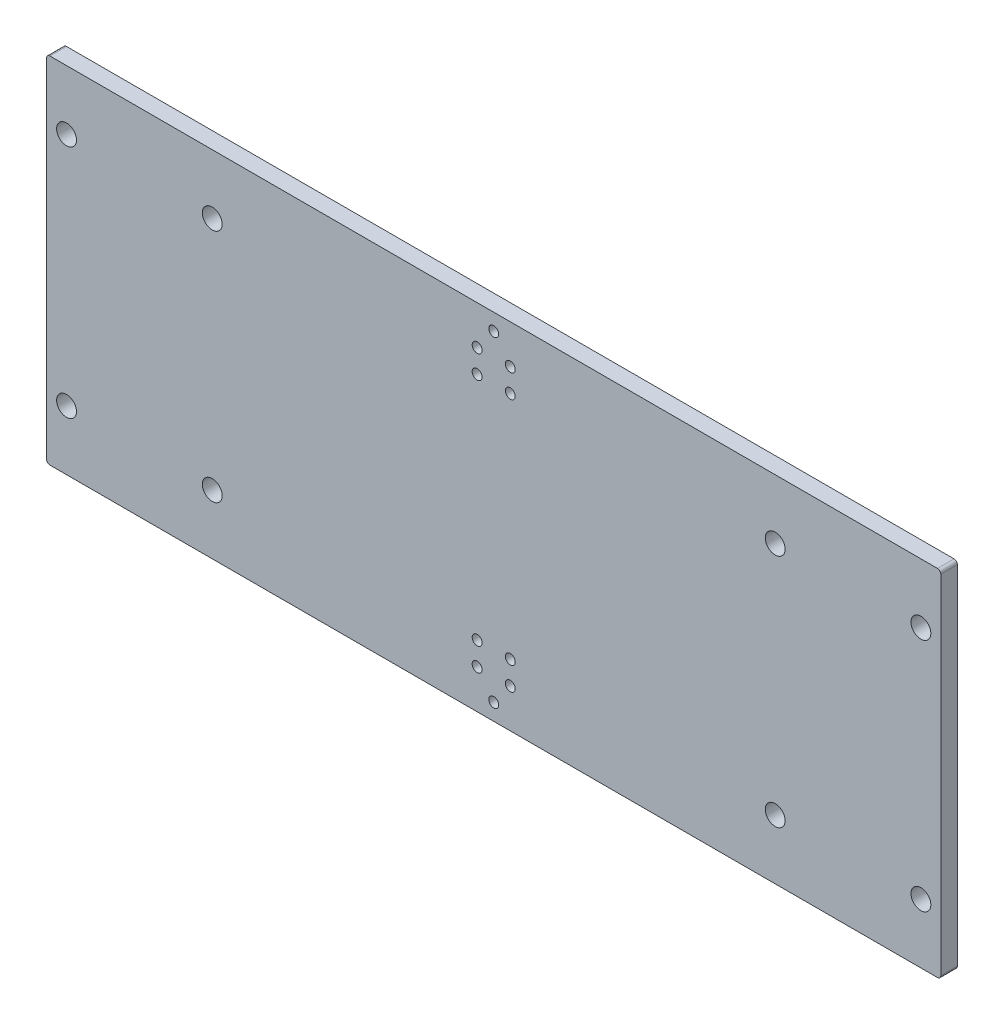
SolidWorks part; units mm, degrees
ref_plane "前视基准面" through (0, 0, 0) normal (0, 0, 1) x (1, 0, 0)
ref_plane "上视基准面" through (0, 0, 0) normal (0, 1, 0) x (1, 0, 0)
ref_plane "右视基准面" through (0, 0, 0) normal (1, 0, 0) x (0, 0, -1)
sketch "草图1" plane through (0, 0, 0) normal (0, 0, 1) x (1, 0, 0)
  line L1 (-135, -53.5) -> (135, -53.5)
  line L2 (-135, -53.5) -> (-135, 53.5)
  line L3 (-135, 53.5) -> (135, 53.5)
  line L4 (135, -53.5) -> (135, 53.5)
  line L5 (-135, -53.5) -> (135, 53.5) construction
  line L6 (-135, 53.5) -> (135, -53.5) construction
  point P0 (0, 0)
  dimension "D1" = 270
  dimension "D2" = 107
base flange "基体-法兰1" sketch "草图1" thickness 5 reverse thickness direction no parameters "D1"=0.7366
sketch "草图6" plane through (0, 0, 0) normal (0, 0, 1) x (1, 0, 0)
  line L0 (-135, 53.5) -> (-135, -53.5) construction
  line L1 (-135, -53.5) -> (135, -53.5) construction
  line L2 (135, 53.5) -> (-135, 53.5) construction
  circle A0 centre (-129, 35.5) radius 3
  circle A1 centre (-129, -35.5) radius 3
  circle A2 centre (-85, 35.5) radius 3
  circle A3 centre (-85, -35.5) radius 3
  dimension "D2" = 6
  dimension "D3" = 6
  dimension "D7" = 6
  dimension "D8" = 6
  dimension "D1" = 6
  dimension "D4" = 6
  dimension "D5" = 18
  dimension "D6" = 18
  dimension "D9" = 44
  dimension "D10" = 44
extrude "切除-拉伸1" cut sketch "草图6" against normal blind 10 normal cut yes
mirror "镜向1" about plane through (0, 0, 0) normal (1, 0, 0) of "切除-拉伸1"
sketch "草图7" plane through (0, 0, 0) normal (0, 0, 1) x (1, 0, 0)
  line L0 (135, 53.5) -> (-135, 53.5) construction
  circle A0 centre (0, 48.5) radius 1.5
  dimension "D1" = 3
  dimension "D2" = 5
extrude "切除-拉伸2" cut sketch "草图7" against normal blind 10 normal cut yes
mirror "镜向2" about plane through (0, 0, 0) normal (0, 1, 0) of "切除-拉伸2"
fillet "圆角1" radius 1 4 edges at (-135, -53.5, -2.5) (-135, 53.5, -2.5) (135, -53.5, -2.5) (135, 53.5, -2.5)
sketch "草图8" plane through (0, 0, -5) normal (0, 0, -1) x (-1, 0, 0)
  line L0 (-134, 53.5) -> (134, 53.5) construction
  circle A0 centre (-5, 41.75) radius 1.5
  circle A1 centre (5, 41.75) radius 1.5
  circle A2 centre (5, 34.75) radius 1.5
  circle A3 centre (-5, 34.75) radius 1.5
  circle A4 centre (0, 48.5) radius 1.5 construction
  dimension "D1" = 3
  dimension "D2" = 3
  dimension "D3" = 3
  dimension "D4" = 3
  dimension "D5" = 11.75
  dimension "D6" = 11.75
  dimension "D7" = 7
  dimension "D8" = 7
  dimension "D9" = 5
  dimension "D10" = 5
extrude "切除-拉伸3" cut sketch "草图8" against normal blind 10 normal cut yes
mirror "镜向3" about plane through (0, 0, 0) normal (0, 1, 0) of "切除-拉伸3"
sketch "折弯-线1" [suppressed] plane through (0, 0, 0) normal (0, 1, 0) x (1, 0, 0)
sketch "边界框1" [suppressed] plane through (0, 0, 0) normal (0, 1, 0) x (1, 0, 0)
sheet metal parameters "钣金1" thickness 5 parameters "D1"=0.7366
flat pattern "平板型式1" [suppressed]
sketch "折弯-线2" plane through (0, 0, 0) normal (0, 1, 0) x (1, 0, 0)
sketch3d "边界框2" [suppressed]
  line L0 (150, -53.5, 0) -> (-150, -53.5, 0) construction
  line L1 (150, 53.5, 0) -> (-150, 53.5, 0) construction
  line L2 (150, -53.5, 0) -> (150, 53.5, 0) construction
  line L3 (-150, -53.5, 0) -> (-150, 53.5, 0) construction
sheet metal parameters "钣金2" thickness 5 parameters "D1"=0.7366
flat pattern "平板型式1"
sketch "折弯-线2" plane through (0, 0, 0) normal (0, 1, 0) x (1, 0, 0)
sketch3d "边界框2" [suppressed]
  line L0 (-150, -53.5, 0) -> (150, -53.5, 0) construction
  line L1 (-150, 53.5, 0) -> (150, 53.5, 0) construction
  line L2 (-150, -53.5, 0) -> (-150, 53.5, 0) construction
  line L3 (150, -53.5, 0) -> (150, 53.5, 0) construction
sheet metal parameters "钣金3" thickness 5 parameters "D1"=0.7366
flat pattern "平板型式1"
sketch "折弯-线2" plane through (0, 0, 0) normal (0, 1, 0) x (1, 0, 0)
sketch3d "边界框2" [suppressed]
  line L0 (-135, -53.5, 0) -> (135, -53.5, 0) construction
  line L1 (-135, 53.5, 0) -> (135, 53.5, 0) construction
  line L2 (-135, -53.5, 0) -> (-135, 53.5, 0) construction
  line L3 (135, -53.5, 0) -> (135, 53.5, 0) construction
sheet metal parameters "钣金4" thickness 5 parameters "D1"=0.7366
flat pattern "平板型式1"
sketch "折弯-线2" plane through (0, 0, 0) normal (0, 1, 0) x (1, 0, 0)
sketch3d "边界框2" [suppressed]
  line L0 (-135, -53.5, 0) -> (135, -53.5, 0) construction
  line L1 (-135, 53.5, 0) -> (135, 53.5, 0) construction
  line L2 (-135, -53.5, 0) -> (-135, 53.5, 0) construction
  line L3 (135, -53.5, 0) -> (135, 53.5, 0) construction
sheet metal parameters "钣金5" thickness 5 parameters "D1"=0.7366
flat pattern "平板型式1"
sketch "折弯-线2" plane through (0, 0, 0) normal (0, 1, 0) x (1, 0, 0)
sketch3d "边界框2" [suppressed]
  line L0 (-135, -53.5, 0) -> (135, -53.5, 0) construction
  line L1 (-135, 53.5, 0) -> (135, 53.5, 0) construction
  line L2 (-135, -53.5, 0) -> (-135, 53.5, 0) construction
  line L3 (135, -53.5, 0) -> (135, 53.5, 0) construction
sheet metal parameters "钣金6" thickness 5 parameters "D1"=0.7366
flat pattern "平板型式1"
sketch "折弯-线2" plane through (0, 0, 0) normal (0, 1, 0) x (1, 0, 0)
sketch3d "边界框2" [suppressed]
  line L0 (-135, -53.5, 0) -> (135, -53.5, 0) construction
  line L1 (-135, 53.5, 0) -> (135, 53.5, 0) construction
  line L2 (-135, -53.5, 0) -> (-135, 53.5, 0) construction
  line L3 (135, -53.5, 0) -> (135, 53.5, 0) construction
sheet metal parameters "钣金7" thickness 5 parameters "D1"=0.7366
flat pattern "平板型式1"
sketch "折弯-线2" plane through (0, 0, 0) normal (0, 1, 0) x (1, 0, 0)
sketch3d "边界框2" [suppressed]
  line L0 (-135, -53.5, 0) -> (135, -53.5, 0) construction
  line L1 (-135, 53.5, 0) -> (135, 53.5, 0) construction
  line L2 (-135, -53.5, 0) -> (-135, 53.5, 0) construction
  line L3 (135, -53.5, 0) -> (135, 53.5, 0) construction
